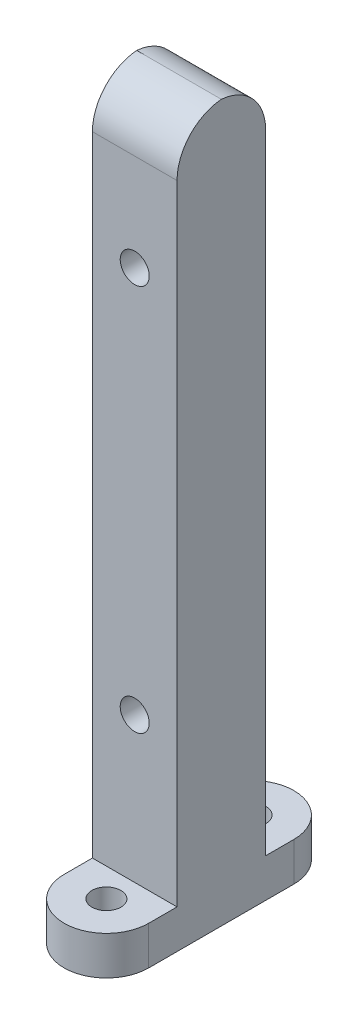
SolidWorks part; units mm, degrees
ref_plane "Front Plane" through (0, 0, 0) normal (0, 0, 1) x (1, 0, 0)
ref_plane "Top Plane" through (0, 0, 0) normal (0, 1, 0) x (1, 0, 0)
ref_plane "Right Plane" through (0, 0, 0) normal (1, 0, 0) x (0, 0, -1)
sketch "Sketch1" plane through (0, 0, 0) normal (0, 1, 0) x (1, 0, 0)
  line L0 (0, 0) -> (0, -15) construction
  line L1 (0, 0) -> (0, -15) construction
  line L2 (4.3723, 0) -> (4.3723, -15)
  line L3 (-4.3723, 0) -> (-4.3723, -15)
  circle A0 centre (0, 0) radius 1.5
  circle A1 centre (0, -15) radius 1.5
  arc A2 (4.3723, 0) -> (-4.3723, 0) centre (0, 0) ccw
  arc A3 (-4.3723, -15) -> (4.3723, -15) centre (0, -15) ccw
  point P5 (0, -7.5)
  dimension "D1" = 15
extrude "Boss-Extrude1" add sketch "Sketch1" along normal blind 4 contours A1 | A0 | L3 A3 L2 A2 region at (0, 0, 0) region at (0, 0, 15)
sketch "Sketch2" plane through (0, 4, 0) normal (0, 1, 0) x (1, 0, 0)
  line L0 (-4.3723, -7.5) -> (4.3723, -7.5) construction
  line L1 (-4.3723, 0) -> (-4.3723, -15) construction
  line L2 (4.3723, 0) -> (4.3723, -15) construction
  line L4 (-4.3723, -2.9243) -> (4.3723, -2.9243)
  line L5 (-4.3723, -2.9243) -> (-4.3723, -12.0757)
  line L6 (-4.3723, -12.0757) -> (4.3723, -12.0757)
  line L7 (4.3723, -2.9243) -> (4.3723, -12.0757)
  line L8 (-4.3723, -2.9243) -> (4.3723, -12.0757) construction
  line L9 (-4.3723, -12.0757) -> (4.3723, -2.9243) construction
  point P6 (0, -7.5)
extrude "Boss-Extrude2" add sketch "Sketch2" along normal blind 70 contours L5 L4 L7 L6
sketch "Sketch6" plane through (0, 0, 12.0757) normal (0, 0, 1) x (1, 0, 0)
  line L0 (0, 74) -> (0, 4) construction
  line L1 (-4.3723, 74) -> (4.3723, 74) construction
  line L2 (-4.3723, 4) -> (4.3723, 4) construction
  line L3 (0, 39) -> (4.3723, 39) construction
  line L4 (4.3723, 74) -> (4.3723, 4) construction
  line L5 (4.3723, 39) -> (4.3723, 59) construction
  line L6 (4.3723, 59) -> (0, 59) construction
  circle A0 centre (0, 59) radius 1.5
  circle A1 centre (0, 19) radius 1.5
  dimension "D1" = 20
fillet "Fillet3" radius 5 2 edges at (0, 74, 2.9243) (0, 74, 12.0757)
extrude "Cut-Extrude2" cut sketch "Sketch6" against normal blind 55
